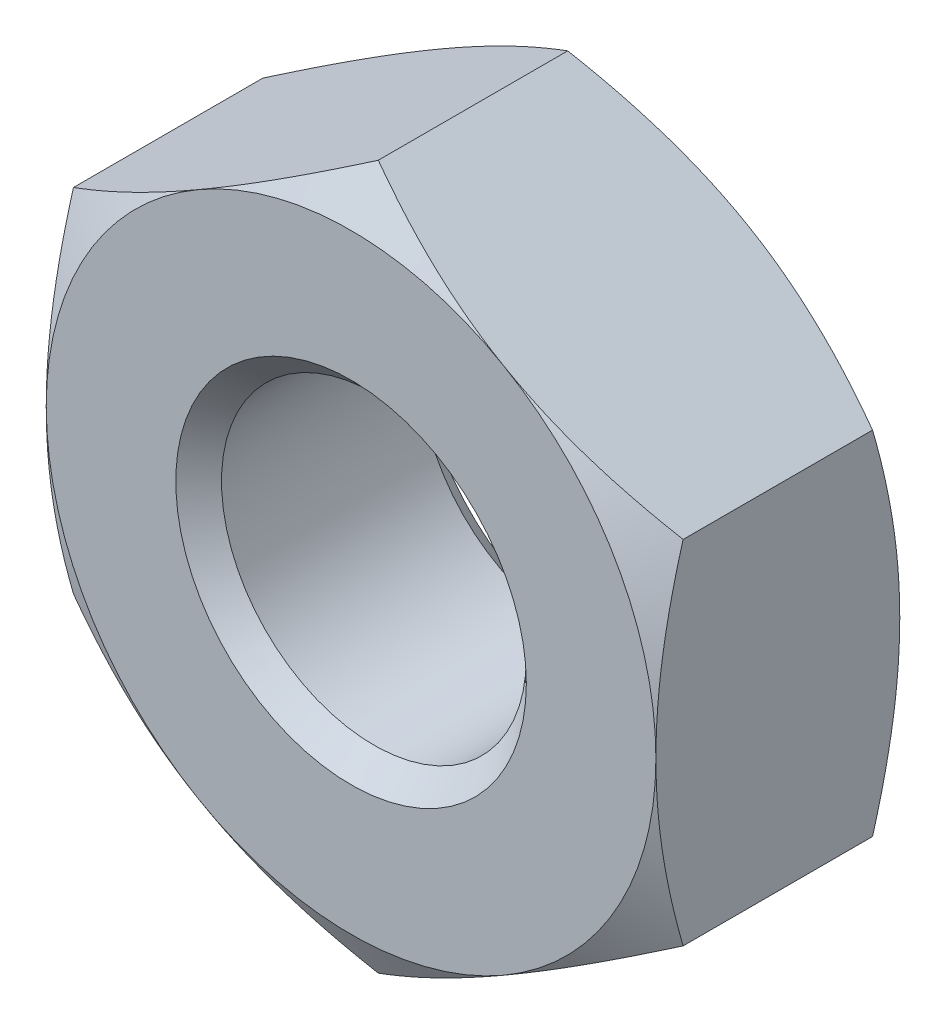
SolidWorks part; units mm, degrees
ref_plane "Front Plane" through (0, 0, 0) normal (0, 0, 1) x (1, 0, 0)
ref_plane "Top Plane" through (0, 0, 0) normal (0, 1, 0) x (1, 0, 0)
ref_plane "Right Plane" through (0, 0, 0) normal (1, 0, 0) x (0, 0, -1)
sketch "Sketch1" plane through (0, 0, 0) normal (0, 0, 1) x (1, 0, 0)
  line L1 (0, 2.3094) -> (-2, 1.1547)
  line L2 (-2, 1.1547) -> (-2, -1.1547)
  line L3 (-2, -1.1547) -> (0, -2.3094)
  line L4 (0, -2.3094) -> (2, -1.1547)
  line L5 (2, -1.1547) -> (2, 1.1547)
  line L6 (2, 1.1547) -> (0, 2.3094)
  circle A0 centre (0, 0) radius 2 construction
  circle A1 centre (0, 0) radius 1
  circle A3 centre (0, 0) radius 3
  dimension "D1" = 6
  dimension "D2" = 4
extrude "Boss-Extrude1" add sketch "Sketch1" along normal blind 1.6 contours A3 L6 L5 L4 L3 L2 L1 | L5 L6 L1 L2 L3 L4 A1 region at (0.9694, 1.6791, 0) region at (-2.9151, 0, 0)
chamfer "Chamfer1" distance 1 angle 30 1 edges at (3, 0, 1.6) first distance on face at (3, 0, 1.6)
chamfer "Chamfer2" distance 1 angle 30 1 edges at (3, 0, 0) first distance on face at (3, 0, 0)
extrude "Cut-Extrude1" cut sketch "Sketch1<3>" along normal through all contours A3 L6 L5 L4 L3 L2 L1 region at (-2.9151, 0, 0)
sketch "Sketch1<3>" plane through (0, 0, 0) normal (0, 0, 1) x (1, 0, 0) same geometry as "Sketch1"
chamfer "Chamfer3" distance 0.15 angle 45 2 edges at (1, 0, 0) (1, 0, 1.6)
